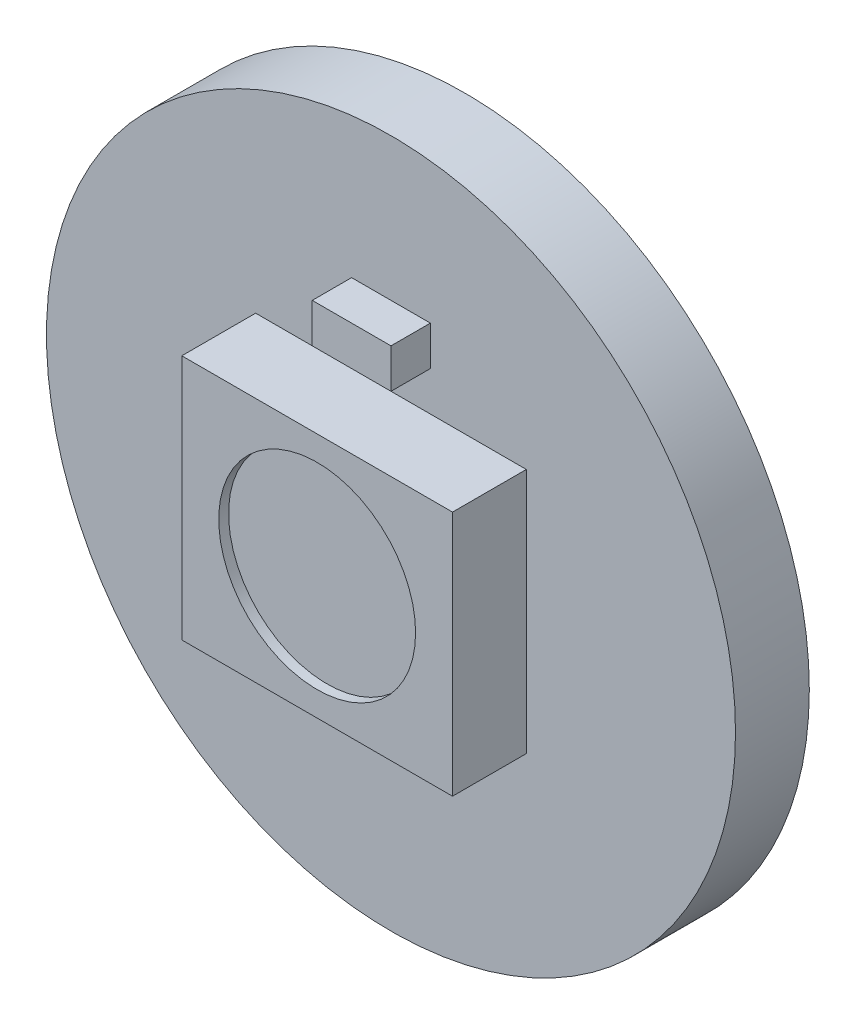
SolidWorks part; units mm, degrees
ref_plane "Front Plane" through (0, 0, 0) normal (0, 0, 1) x (1, 0, 0)
ref_plane "Top Plane" through (0, 0, 0) normal (0, 1, 0) x (1, 0, 0)
ref_plane "Right Plane" through (0, 0, 0) normal (1, 0, 0) x (0, 0, -1)
sketch "Sketch1" plane through (0, 0, 0) normal (0, 0, 1) x (1, 0, 0)
  circle A0 centre (0, 0) radius 7
  dimension "D1" = 14
extrude "Boss-Extrude1" add sketch "Sketch1" along normal blind 1.5
sketch "Sketch2" plane through (0, 0, 1.5) normal (0, 0, 1) x (1, 0, 0)
  line L1 (-2.75, 2.5) -> (2.75, 2.5)
  line L2 (-2.75, 2.5) -> (-2.75, -2.5)
  line L3 (-2.75, -2.5) -> (2.75, -2.5)
  line L4 (2.75, 2.5) -> (2.75, -2.5)
  line L5 (-2.75, 2.5) -> (2.75, -2.5) construction
  line L6 (-2.75, -2.5) -> (2.75, 2.5) construction
  point P0 (0, 0)
  dimension "D1" = 5
  dimension "D2" = 5.5
extrude "Boss-Extrude2" add sketch "Sketch2" along normal blind 1.5
sketch "Sketch3" plane through (0, 0, 3) normal (0, 0, 1) x (1, 0, 0)
  circle A0 centre (0, 0) radius 2
  dimension "D1" = 4
extrude "Cut-Extrude1" cut sketch "Sketch3" against normal blind 0.2
sketch "Sketch4" plane through (0, 0, 1.5) normal (0, 0, 1) x (1, 0, 0)
  line L0 (0, 3.7) -> (0, 0) construction
  line L1 (-0.8, 4.1) -> (0.8, 4.1)
  line L2 (-0.8, 4.1) -> (-0.8, 3.3)
  line L3 (-0.8, 3.3) -> (0.8, 3.3)
  line L4 (0.8, 4.1) -> (0.8, 3.3)
  line L5 (-0.8, 4.1) -> (0.8, 3.3) construction
  line L6 (-0.8, 3.3) -> (0.8, 4.1) construction
  point P0 (0, 3.7)
  dimension "D1" = 3.7
  dimension "D2" = 1.6
  dimension "D3" = 0.8
extrude "Boss-Extrude3" add sketch "Sketch4" along normal blind 0.8
ref_axis "Axis1" through (0, 0, -0.15) along (0, 0, 1)
